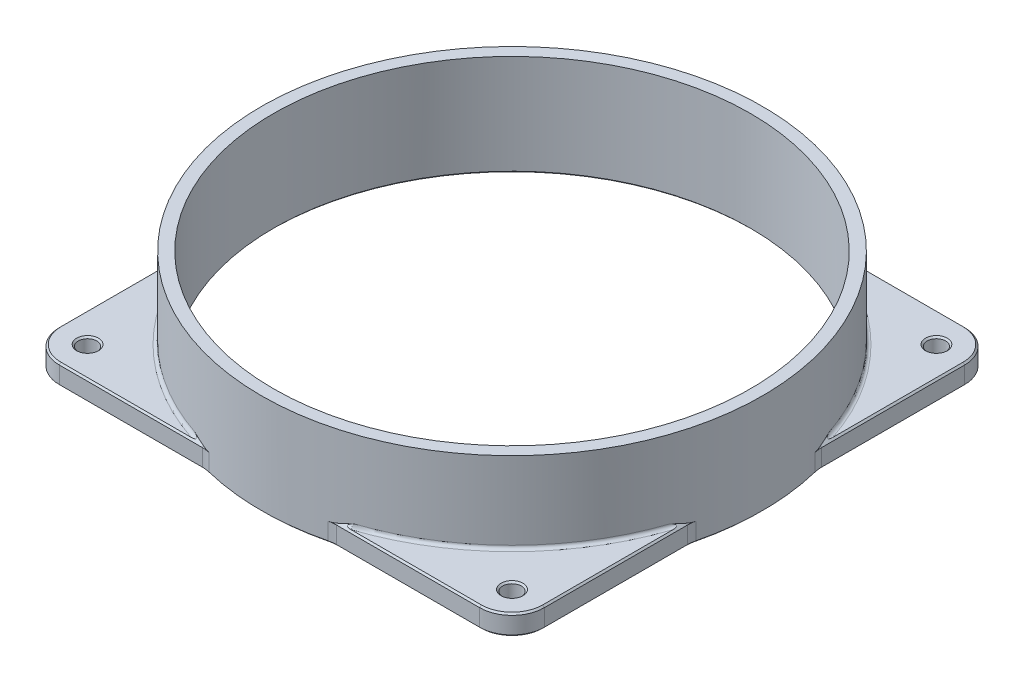
SolidWorks part; units mm, degrees
ref_plane "前视基准面" through (0, 0, 0) normal (0, 0, 1) x (1, 0, 0)
ref_plane "上视基准面" through (0, 0, 0) normal (0, 1, 0) x (1, 0, 0)
ref_plane "右视基准面" through (0, 0, 0) normal (1, 0, 0) x (0, 0, -1)
other "Configuration Table"
sketch "草图1" plane through (0, 0, 0) normal (0, 1, 0) x (1, 0, 0)
  line L8 (75.6205, 0) -> (120, 0)
  line L9 (0, 0) -> (44.3795, 0)
  line L10 (0, 0) -> (0, -44.3795)
  line L11 (0, -120) -> (44.3795, -120)
  line L12 (120, 0) -> (120, -44.3795)
  line L13 (120, -75.6205) -> (120, -120)
  line L14 (75.6205, -120) -> (120, -120)
  line L15 (0, -75.6205) -> (0, -120)
  circle A0 centre (7.5, -112.5) radius 2.3
  circle A1 centre (112.5, -112.5) radius 2.3
  circle A2 centre (112.5, -7.5) radius 2.3
  circle A3 centre (7.5, -7.5) radius 2.3
  circle A4 centre (60, -60) radius 59
  arc A5 (0, -44.3795) -> (0, -75.6205) centre (60, -60) ccw
  arc A6 (75.6205, 0) -> (44.3795, 0) centre (60, -60) ccw
  arc A7 (120, -75.6205) -> (120, -44.3795) centre (60, -60) ccw
  arc A8 (44.3795, -120) -> (75.6205, -120) centre (60, -60) ccw
  dimension "D3" = 4.6
  dimension "D10" = 118
  dimension "D1" = 120
  dimension "D2" = 120
  dimension "D4" = 7.5
  dimension "D5" = 7.5
  dimension "D8" = 60
  dimension "D9" = 60
  dimension "D11" = 3
  dimension "D6" = 2
  dimension "D7" = 2
extrude "凸台-拉伸2" add sketch "草图1" along normal blind 5
sketch "草图2" plane through (0, 5, 0) normal (0, 1, 0) x (1, 0, 0)
  circle A0 centre (60, -60) radius 59
  circle A2 centre (60, -60) radius 62
extrude "凸台-拉伸3" add sketch "草图2" along normal blind 20
fillet "圆角1" radius 8 12 edges at (44.3795, 2.5, 0) (75.6205, 2.5, 0) (120, 2.5, 0) (120, 2.5, 44.3795) (120, 2.5, 75.6205) (120, 2.5, 120) (75.6205, 2.5, 120) (44.3795, 2.5, 120) (0, 2.5, 120) (0, 2.5, 75.6205) (0, 2.5, 44.3795) (0, 2.5, 0)
chamfer "倒角1" distance 0.4 angle 45 29 edges at (7.5, 0, 9.8) (112.5, 0, 9.8) (112.5, 0, 114.8) (60, 0, 119) (7.5, 0, 114.8) (75.6571, 0, -0.0573) (60, 0, -2) (44.3429, 0, -0.0573) (25.6934, 0, 0) (2.3431, 0, 2.3431) (0, 0, 25.6934) (-0.0573, 0, 44.3429) (-2, 0, 60) (-0.0573, 0, 75.6571) (0, 0, 94.3066) (2.3431, 0, 117.6569) (25.6934, 0, 120) (44.3429, 0, 120.0573) (60, 0, 122) (75.6571, 0, 120.0573) (94.3066, 0, 120) (117.6569, 0, 117.6569) (120, 0, 94.3066) (120.0573, 0, 75.6571) (122, 0, 60) (120.0573, 0, 44.3429) (120, 0, 25.6934) (117.6569, 0, 2.3431) (94.3066, 0, 0)
chamfer "倒角3" distance 0.4 angle 45 24 edges at (112.5, 5, 114.8) (75.6571, 5, 120.0573) (94.3066, 5, 120) (117.6569, 5, 117.6569) (120.0573, 5, 75.6571) (120, 5, 94.3066) (112.5, 5, 9.8) (120.0573, 5, 44.3429) (120, 5, 25.6934) (117.6569, 5, 2.3431) (75.6571, 5, -0.0573) (94.3066, 5, 0) (7.5, 5, 9.8) (44.3429, 5, -0.0573) (25.6934, 5, 0) (2.3431, 5, 2.3431) (-0.0573, 5, 44.3429) (0, 5, 25.6934) (7.5, 5, 114.8) (44.3429, 5, 120.0573) (25.6934, 5, 120) (-0.0573, 5, 75.6571) (2.3431, 5, 117.6569) (0, 5, 94.3066)
fillet "圆角3" radius 0.8 4 edges at (103.8406, 5, 16.1594) (103.8406, 5, 103.8406) (16.1594, 5, 103.8406) (16.1594, 5, 16.1594)
equation "\"D4@草图1\"=(120-105)/2"
equation "\"D5@草图1\"=\"D4@草图1\""
